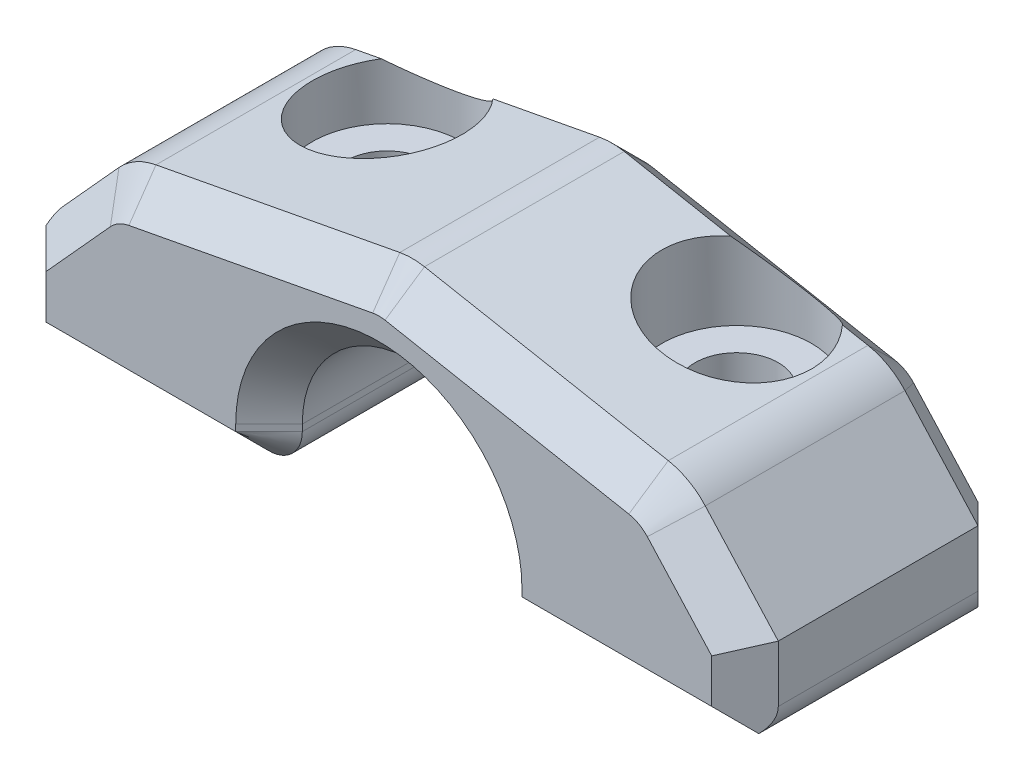
SolidWorks part; units mm, degrees
ref_plane "Front Plane" through (0, 0, 0) normal (0, 0, 1) x (1, 0, 0)
ref_plane "Top Plane" through (0, 0, 0) normal (0, 1, 0) x (1, 0, 0)
ref_plane "Right Plane" through (0, 0, 0) normal (1, 0, 0) x (0, 0, -1)
sketch "Sketch1" plane through (0, 0, 0) normal (0, 0, 1) x (1, 0, 0)
  line L0 (-3.3, 0) -> (-11, 0)
  line L1 (-11, 0) -> (-11, 6)
  line L2 (-11, 6) -> (11, 6)
  line L3 (0, 6) -> (0, 3.3) construction
  line L4 (11, 0) -> (11, 6)
  line L5 (3.3, 0) -> (11, 0)
  arc A0 (3.3, 0) -> (-3.3, 0) centre (0, 0) ccw
  dimension "D1" = 6.6
  dimension "D2" = 22
  dimension "D3" = 6
extrude "Boss-Extrude1" add sketch "Sketch1" along normal blind 8
sketch "Sketch2" plane through (0, 0, 8) normal (0, 0, 1) x (1, 0, 0)
  line L0 (0, 6) -> (-8.3557, 4.4229)
  line L1 (11, 6) -> (-11, 6) construction
  line L2 (-8.3557, 4.4229) -> (-11, 1.5044)
  line L3 (-11, 6) -> (-11, 0) construction
  line L4 (-11, 1.5044) -> (-11, 6)
  line L5 (-11, 6) -> (11, 6)
  line L6 (0, 8.1862) -> (0, -3.9101) construction
  line L7 (11, 1.5044) -> (11, 6)
  line L8 (8.3557, 4.4229) -> (11, 1.5044)
  line L9 (0, 6) -> (8.3557, 4.4229)
  line L10 (-11, 0) -> (-3.3, 0) construction
  line M8 (11, 0) -> (11, 6)
  line M9 (11, 6) -> (-11, 6)
  line M10 (-11, 6) -> (-11, 0)
  dimension "D1" = 4.4229
  dimension "D2" = 16.7114
  dimension "D3" = 4.4956
extrude "Cut-Extrude1" cut sketch "Sketch2" against normal through all both and the other way through all contours L2 L0 M9 M10 | L9 L8 M9 M8 region at (-7.9428, 4.865, 8) region at (7.9428, 4.865, 8)
sketch "Sketch3" plane through (0, 0, 8) normal (0, 0, 1) x (1, 0, 0)
  line L0 (-3.3, 0) -> (-3.3, -1.1963)
  line L1 (-3.3, -1.1963) -> (-11, -1.1963)
  line L2 (-11, -1.1963) -> (-11, 0)
  line L3 (-11, 0) -> (-3.3, 0)
  line L4 (0, 2.4166) -> (0, -1.9705) construction
  line L5 (11, 0) -> (3.3, 0)
  line L6 (11, -1.1963) -> (11, 0)
  line L7 (3.3, -1.1963) -> (11, -1.1963)
  line L8 (3.3, 0) -> (3.3, -1.1963)
extrude "Boss-Extrude2" add sketch "Sketch3" against normal up to surface (8 mm away) up to face at (0, 2.3505, 0)
chamfer "Chamfer1" distance 1 angle 45 4 edges at (-11, 0.1541, 0) (11, 0.1541, 0) (11, 0.1541, 8) (-11, 0.1541, 8)
fillet "Fillet1" radius 1 2 edges at (3.3, -1.1963, 4) (-3.3, -1.1963, 4)
sketch "Sketch4" plane through (0, -1.1963, 0) normal (0, -1, 0) x (1, 0, 0)
  line L0 (0, 10.0567) -> (0, -3.4815) construction
  line L1 (-5.25, 2.5) -> (5.25, 2.5) construction
  line L2 (-3.3, 0) -> (3.3, 0) construction
  circle A0 centre (-5.25, 2.5) radius 1.25
  circle A1 centre (5.25, 2.5) radius 1.25
  point P7 (6.768, 1.3051)
  point P8 (0, 2.5)
  dimension "D2" = 2.5
  dimension "D1" = 10.5
  dimension "D3" = 2.5
extrude "Cut-Extrude2" cut sketch "Sketch4" against normal through all
sketch "Sketch5" plane through (0, 0, 0) normal (0, 1, 0) x (1, 0, 0)
  circle A0 centre (-5.25, -2.5) radius 2.25
  circle A1 centre (5.25, -2.5) radius 2.25
  dimension "D1" = 4.5
extrude "Cut-Extrude3" cut sketch "Sketch5" along normal blind 10 from offset 3
fillet "Fillet2" radius 2 4 edges at (8.3557, 4.4229, 4) (-8.3557, 4.4229, 4) (-11, 1.5044, 4)
fillet "Fillet3" radius 1 2 edges at (11, -1.1963, 4) (-11, -1.1963, 4)
chamfer "Chamfer2" distance 1 angle 45 28 edges at (-9.4034, 3.2666, 0) (-8.302, 4.3271, 0) (-4.0333, 5.2388, 0) (9.4034, 3.2666, 0) (0, 5.9647, 0) (8.302, 4.3271, 0) (4.0333, 5.2388, 0) (-7.15, -1.1963, 0) (7.15, -1.1963, 0) (-3.5929, -0.9034, 0) (3.5929, -0.9034, 0) (-3.3, -0.0982, 0) (3.3, -0.0982, 0) (0, 3.3, 0) (-7.15, -1.1963, 8) (7.15, -1.1963, 8) (-3.5929, -0.9034, 8) (3.5929, -0.9034, 8) (-3.3, -0.0982, 8) (3.3, -0.0982, 8) (0, 3.3, 8) (9.4034, 3.2666, 8) (8.302, 4.3271, 8) (-9.4034, 3.2666, 8) (0, 5.9647, 8) (-8.302, 4.3271, 8)
